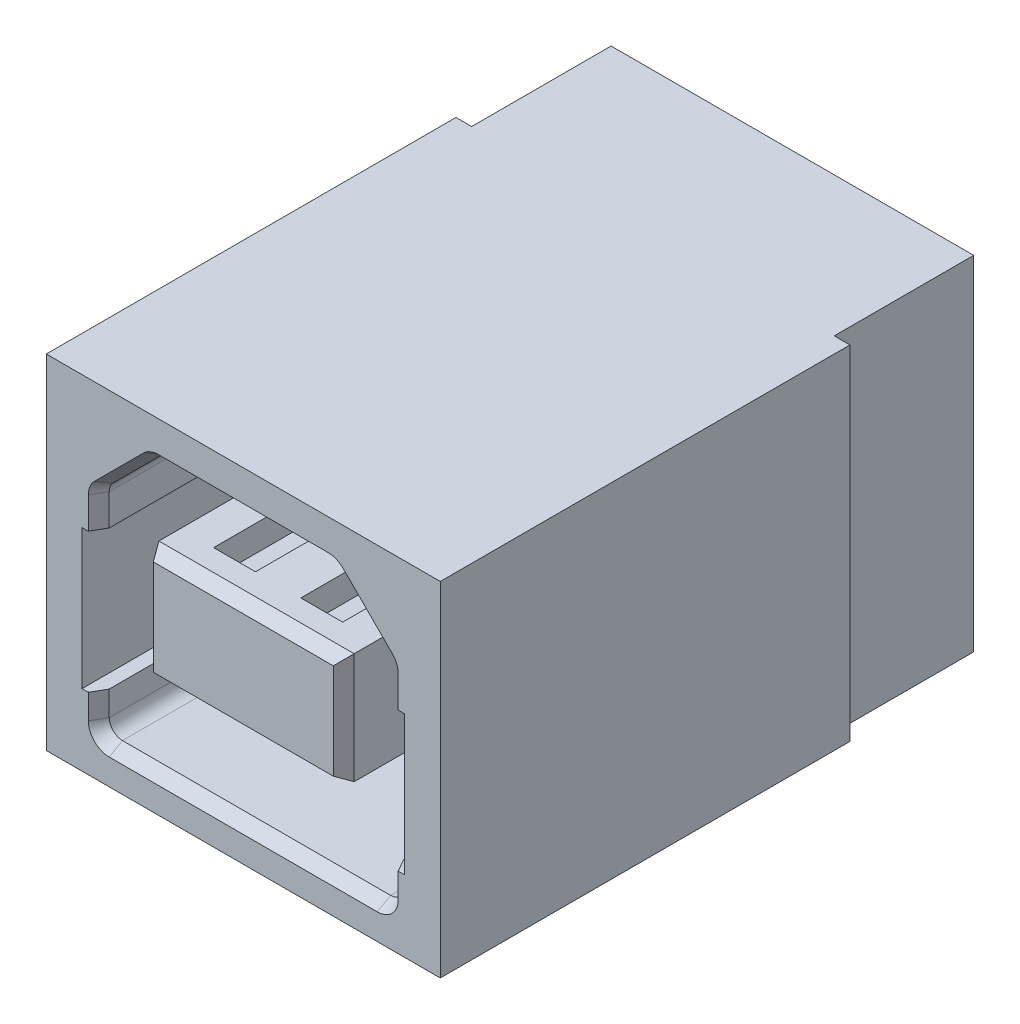
SolidWorks part; units mm, degrees
material "PTFE (general)"
ref_plane "Front Plane" through (0, 0, 0) normal (0, 0, 1) x (1, 0, 0)
ref_plane "Top Plane" through (0, 0, 0) normal (0, 1, 0) x (1, 0, 0)
ref_plane "Right Plane" through (0, 0, 0) normal (1, 0, 0) x (0, 0, -1)
ref_plane "Plane1" through (0, 0, -0.38) normal (0, 0, 1) x (1, 0, 0)
sketch "Sketch1" plane through (0, 0, -0.38) normal (0, 0, 1) x (1, 0, 0)
  line L0 (55, 0) -> (-55, 0) construction
  line L1 (-5.65, 10.25) -> (5.65, 10.25)
  line L2 (-5.65, 10.25) -> (-5.65, 0.4)
  line L3 (-5.65, 0.4) -> (5.65, 0.4)
  line L4 (5.65, 10.25) -> (5.65, 0.4)
  line L5 (0, -55) -> (0, 55) construction
  dimension "D1" = 11.3
  dimension "D2" = 10.25
  dimension "D3" = 0.4
  dimension "D4" = 5.65
extrude "Boss-Extrude1" add sketch "Sketch1" against normal blind 15.75
sketch "Sketch2" plane through (0, 10.25, 0) normal (0, 1, 0) x (1, 0, 0)
  line L0 (0, -55) -> (0, 55) construction
  line L1 (-5.65, 16.13) -> (-5.2, 16.13)
  line L2 (-5.65, 16.13) -> (-5.65, 12.13)
  line L3 (-5.65, 12.13) -> (-5.2, 12.13)
  line L4 (-5.2, 16.13) -> (-5.2, 12.13)
  line L5 (5.65, 16.13) -> (5.2, 16.13)
  line L6 (5.65, 16.13) -> (5.65, 12.13)
  line L7 (5.65, 12.13) -> (5.2, 12.13)
  line L8 (5.2, 16.13) -> (5.2, 12.13)
  dimension "D1" = 10.4
  dimension "D2" = 5.2
  dimension "D3" = 4
extrude "Cut-Extrude1" cut sketch "Sketch2" against normal blind 15.75
sketch "Sketch3" plane through (0, 0, -0.38) normal (0, 0, 1) x (1, 0, 0)
  line L0 (-5.65, 4.45) -> (5.65, 4.45) construction
  line L1 (-5.65, 10.25) -> (-5.65, 0.4) construction
  line L2 (5.65, 0.4) -> (5.65, 10.25) construction
  line L3 (55, 0) -> (-55, 0) construction
  line L4 (-4.225, 7.3526) -> (-4.225, 6.45)
  line L5 (-3.845, 1.36) -> (3.845, 1.36)
  line L6 (4.225, 1.74) -> (4.225, 2.45)
  line L7 (4.1137, 7.6213) -> (2.7063, 9.0287)
  line L8 (2.4376, 9.14) -> (-2.4376, 9.14)
  line L9 (-2.7063, 9.0287) -> (-4.1137, 7.6213)
  line L10 (0, -55) -> (0, 55) construction
  line L11 (-2.8, 5.25) -> (2.8, 5.25) construction
  line L12 (-2.8, 6.84) -> (2.8, 6.84)
  line L13 (-2.8, 6.84) -> (-2.8, 3.66)
  line L14 (-2.8, 3.66) -> (2.8, 3.66)
  line L15 (2.8, 6.84) -> (2.8, 3.66)
  line L16 (-4.225, 2.45) -> (-4.225, 1.74)
  line L17 (4.225, 6.45) -> (4.625, 6.45)
  line L19 (4.225, 2.45) -> (4.625, 2.45)
  line L20 (4.625, 6.45) -> (4.625, 2.45)
  line L21 (-4.225, 6.45) -> (-4.625, 6.45)
  line L22 (4.225, 6.45) -> (4.225, 7.3526)
  line L23 (-4.225, 2.45) -> (-4.625, 2.45)
  line L24 (-4.625, 6.45) -> (-4.625, 2.45)
  arc A0 (-4.225, 7.3526) -> (-4.1137, 7.6213) centre (-3.845, 7.3526) cw
  arc A1 (-2.4376, 9.14) -> (-2.7063, 9.0287) centre (-2.4376, 8.76) ccw
  arc A2 (2.7063, 9.0287) -> (2.4376, 9.14) centre (2.4376, 8.76) ccw
  arc A3 (4.225, 7.3526) -> (4.1137, 7.6213) centre (3.845, 7.3526) ccw
  arc A4 (3.845, 1.36) -> (4.225, 1.74) centre (3.845, 1.74) ccw
  arc A5 (-4.225, 1.74) -> (-3.845, 1.36) centre (-3.845, 1.74) ccw
  point P24 (-4.225, 7.51)
  point P31 (4.225, 7.51)
  dimension "D16" = 0.38
  dimension "D2" = 135
  dimension "D3" = 4.225
  dimension "D4" = 8.45
  dimension "D5" = 7.78
  dimension "D6" = 1.63
  dimension "D7" = 5.6
  dimension "D8" = 2.8
  dimension "D9" = 3.18
  dimension "D10" = 0.8
  dimension "D11" = 5.25
  dimension "D12" = 4.45
  dimension "D13" = 2.3
  dimension "D14" = 2.3
  dimension "D15" = 1.36
  dimension "D17" = 0.4
  dimension "D18" = 4
  dimension "D19" = 2
extrude "Cut-Extrude2" cut sketch "Sketch3" against normal blind 8.38
chamfer "Chamfer1" distance 0.38 angle 30 4 edges at (0, 3.66, -0.38) (2.8, 5.25, -0.38) (0, 6.84, -0.38) (-2.8, 5.25, -0.38) first distance on face at (0, 3.66, -4.57) first distance on face at (2.8, 5.25, -4.57) first distance on face at (0, 6.84, -4.57) first distance on face at (-2.8, 5.25, -4.57)
chamfer "Chamfer2" distance 0.38 angle 30 14 edges at (4.225, 2.095, -0.38) (4.1137, 1.4713, -0.38) (0, 1.36, -0.38) (-4.1137, 1.4713, -0.38) (-4.225, 2.095, -0.38) (4.225, 6.9013, -0.38) (4.1961, 7.498, -0.38) (3.41, 8.325, -0.38) (2.583, 9.1111, -0.38) (0, 9.14, -0.38) (-2.583, 9.1111, -0.38) (-3.41, 8.325, -0.38) (-4.1961, 7.498, -0.38) (-4.225, 6.9013, -0.38) first distance on face at (4.225, 2.095, -4.57) first distance on face at (4.0744, 1.5106, -4.57) first distance on face at (0, 1.36, -4.57) first distance on face at (-4.0744, 1.5106, -4.57) first distance on face at (-4.225, 2.095, -4.57) first distance on face at (4.225, 6.9013, -4.57) first distance on face at (4.1827, 7.4925, -4.57) first distance on face at (3.41, 8.325, -4.57) first distance on face at (2.5775, 9.0977, -4.57) first distance on face at (0, 9.14, -4.57) first distance on face at (-2.5775, 9.0977, -4.57) first distance on face at (-3.41, 8.325, -4.57) first distance on face at (-4.1827, 7.4925, -4.57) first distance on face at (-4.225, 6.9013, -4.57)
sketch "Sketch4" plane through (0, 0.4, 0) normal (0, -1, 0) x (-1, 0, 0)
  line L0 (5.2, 16.13) -> (-5.2, 16.13) construction
  line L1 (4.25, 6) -> (3.25, 6)
  line L2 (4.25, 6) -> (4.25, 16.13)
  line L3 (4.25, 16.13) -> (3.25, 16.13)
  line L4 (3.25, 6) -> (3.25, 16.13)
  line L5 (-5.4175, 0) -> (5.4175, 0) construction
  line L6 (0.5, 7.5) -> (-0.5, 7.5)
  line L7 (0.5, 7.5) -> (0.5, 16.13)
  line L8 (0.5, 16.13) -> (-0.5, 16.13)
  line L9 (-0.5, 7.5) -> (-0.5, 16.13)
  line L10 (-3.25, 6) -> (-4.25, 6)
  line L11 (-3.25, 6) -> (-3.25, 16.13)
  line L12 (-3.25, 16.13) -> (-4.25, 16.13)
  line L13 (-4.25, 6) -> (-4.25, 16.13)
  line L14 (0, 5.4175) -> (0, -5.4175) construction
  dimension "D1" = 1
  dimension "D2" = 6
  dimension "D3" = 0.5
  dimension "D4" = 8.5
  dimension "D5" = 4.25
  dimension "D6" = 1.5
extrude "Boss-Extrude2" add sketch "Sketch4" along normal blind 0.83
ref_plane "Plane2" through (0, 0, -1.38) normal (0, 0, 1) x (1, 0, 0)
sketch "Sketch5" plane through (0, 0, -1.38) normal (0, 0, 1) x (1, 0, 0)
  line L0 (-2.8, 6.84) -> (2.8, 6.84) construction
  line L1 (-1.85, 6.84) -> (-0.65, 6.84)
  line L2 (-1.85, 6.84) -> (-1.85, 6.09)
  line L3 (-1.85, 6.09) -> (-0.65, 6.09)
  line L4 (-0.65, 6.84) -> (-0.65, 6.09)
  line L5 (-2.8, 3.66) -> (2.8, 3.66) construction
  line L6 (0.65, 6.84) -> (1.85, 6.84)
  line L7 (0.65, 6.84) -> (0.65, 6.09)
  line L8 (0.65, 6.09) -> (1.85, 6.09)
  line L9 (1.85, 6.84) -> (1.85, 6.09)
  line L10 (0.65, 3.66) -> (1.85, 3.66)
  line L11 (0.65, 3.66) -> (0.65, 4.41)
  line L12 (0.65, 4.41) -> (1.85, 4.41)
  line L13 (1.85, 3.66) -> (1.85, 4.41)
  line L14 (2.8, 3.66) -> (-2.8, 3.66) construction
  line L15 (-1.85, 3.66) -> (-0.65, 3.66)
  line L16 (-1.85, 3.66) -> (-1.85, 4.41)
  line L17 (-1.85, 4.41) -> (-0.65, 4.41)
  line L18 (-0.65, 3.66) -> (-0.65, 4.41)
  line L20 (-1.25, 6.84) -> (-1.25, 3.66) construction
  line L21 (1.25, 6.84) -> (1.25, 3.66) construction
  line L22 (0, -5.874) -> (0, 5.874) construction
  dimension "D1" = 1.2
  dimension "D2" = 1.25
  dimension "D3" = 1.25
  dimension "D4" = 0.75
extrude "Cut-Extrude3" cut sketch "Sketch5" against normal through all
sketch "Sketch6" plane through (0, 0, -16.13) normal (0, 0, -1) x (-1, 0, 0)
  line L0 (-0.5, 0.4) -> (-3.25, 0.4) construction
  line L1 (-1.85, 6.84) -> (-0.65, 6.84)
  line L2 (-1.85, 6.84) -> (-1.85, 0.4)
  line L3 (-1.85, 0.4) -> (-0.65, 0.4)
  line L4 (-0.65, 6.84) -> (-0.65, 0.4)
  line L5 (-0.65, 6.84) -> (-0.65, 6.09) construction
  line L6 (0.65, 6.84) -> (1.85, 6.84)
  line L7 (0.65, 6.84) -> (0.65, 0.4)
  line L8 (0.65, 0.4) -> (1.85, 0.4)
  line L9 (1.85, 6.84) -> (1.85, 0.4)
  line L10 (1.85, 6.84) -> (1.85, 6.09) construction
  line L11 (3.25, 0.4) -> (0.5, 0.4) construction
extrude "Cut-Extrude4" cut sketch "Sketch6" against normal blind 1.29
sketch "Sketch7" plane through (0, 0, -14.84) normal (0, 0, -1) x (-1, 0, 0)
  line L0 (-0.65, 0.4) -> (-0.65, 3.66) construction
  line L1 (1.85, 3.66) -> (0.65, 3.66) construction
  line L2 (-1.55, 2.66) -> (-1.55, 0)
  line L3 (-1.55, 0) -> (-0.95, 0)
  line L4 (-0.95, 2.66) -> (-0.95, 0)
  line L5 (-0.95, 2.66) -> (-0.65, 2.66)
  line L6 (0.95, 2.66) -> (0.95, 0)
  line L7 (0.95, 0) -> (1.55, 0)
  line L8 (1.55, 2.66) -> (1.55, 0)
  line L12 (1.85, 6.84) -> (1.85, 0.4) construction
  line L13 (0.65, 4.41) -> (1.85, 4.41)
  line L14 (0.65, 4.41) -> (0.65, 2.66)
  line L15 (0.65, 2.66) -> (0.95, 2.66)
  line L16 (1.85, 4.41) -> (1.85, 2.66)
  line L17 (-1.85, 0.4) -> (-1.85, 6.84) construction
  line L18 (-1.85, 4.41) -> (-0.65, 4.41)
  line L19 (-1.85, 4.41) -> (-1.85, 2.66)
  line L20 (-1.85, 2.66) -> (-1.55, 2.66)
  line L21 (-0.65, 4.41) -> (-0.65, 2.66)
  line L22 (1.55, 2.66) -> (1.85, 2.66)
  line L23 (-1.85, 4.41) -> (-0.65, 4.41) construction
  dimension "D1" = 0.3
  dimension "D2" = 0.6
  dimension "D3" = 2.5
  dimension "D4" = 2.66
  dimension "D5" = 1
extrude "Cut-Extrude5" cut sketch "Sketch7" against normal blind 2
